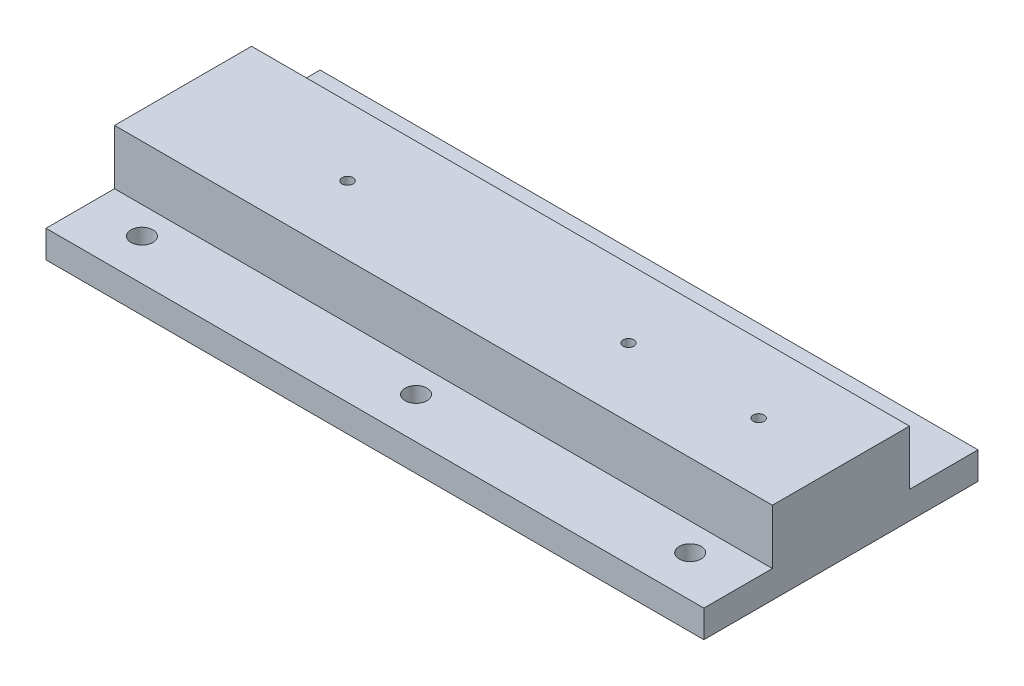
SolidWorks part; units mm, degrees
ref_plane "Front Plane" through (0, 0, 0) normal (0, 0, 1) x (1, 0, 0)
ref_plane "Top Plane" through (0, 0, 0) normal (0, 1, 0) x (1, 0, 0)
ref_plane "Right Plane" through (0, 0, 0) normal (1, 0, 0) x (0, 0, -1)
sketch "Sketch2" plane through (0, 0, 0) normal (0, 1, 0) x (1, 0, 0)
  line L0 (-46.8981, 34.5466) -> (-46.8981, -15.4534)
  line L1 (-46.8981, -15.4534) -> (73.1019, -15.4534)
  line L2 (73.1019, -15.4534) -> (73.1019, 34.5466)
  line L3 (73.1019, 34.5466) -> (-46.8981, 34.5466)
  dimension "D1" = 120
  dimension "D2" = 50
extrude "Boss-Extrude1" add sketch "Sketch2" along normal blind 15
sketch "Sketch3" plane through (0, 0, 0) normal (0, 1, 0) x (1, 0, 0)
  line L0 (74.3548, 9.5466) -> (-56.2815, 9.5466) construction
  line L1 (63.1019, 9.5466) -> (63.1019, 17.0466)
  line L2 (63.1019, 17.0466) -> (3.1019, 17.0466)
  line L3 (3.1019, 17.0466) -> (3.1019, 19.5466)
  line L4 (3.1019, 19.5466) -> (-36.8981, 19.5466)
  line L5 (-36.8981, 19.5466) -> (-36.8981, 9.5466)
  line L6 (-36.8981, 9.5466) -> (63.1019, 9.5466)
  line L7 (73.1019, -15.4534) -> (73.1019, 34.5466) construction
  line L9 (-46.8981, -15.4534) -> (73.1019, -15.4534) construction
  dimension "D1" = 60
  dimension "D2" = 40
  dimension "D3" = 10
  dimension "D4" = 25
  dimension "D5" = 10
  dimension "D6" = 7.5
revolve "Cut-Revolve8" cut sketch "Sketch3" angle 360 about L0
ref_plane "Ebene1" through (63.1019, 0, 0) normal (-1, 0, 0) x (0, 0, 1)
sketch "Skizze2" plane through (63.1019, 0, 0) normal (-1, 0, 0) x (0, 0, 1)
  line L0 (-22.101, 0) -> (5.7524, 0) construction
  line L1 (-2.0466, 0) -> (-17.0466, 0) construction
  line L2 (-9.5466, -15.2765) -> (-9.5466, 13.7911) construction
  line L3 (-4.5466, 0) -> (-2.0466, 0)
  line L5 (-34.5466, 15) -> (-34.5466, 0) construction
  line L6 (15.4534, 15) -> (15.4534, 0) construction
  line L7 (-6.3324, 3.83) -> (-4.7313, 5.75)
  arc A0 (-2.0466, 0) -> (-4.7313, 5.75) centre (-9.5466, 0) ccw
  arc A1 (-4.5466, 0) -> (-6.3324, 3.83) centre (-9.5466, 0) ccw
  dimension "D1" = 5.75
  dimension "D2" = 7.5
  dimension "D3" = 2.5
  dimension "D4" = 3.83
ref_plane "Ebene2" through (28.1019, 0, 0) normal (-1, 0, 0) x (0, 0, 1)
extrude "Aufsatz-Linear austragen3" add sketch "Skizze2" along normal blind 47.5
ref_plane "Ebene3" through (0, 0, -9.5466) normal (0, 0, 1) x (1, 0, 0)
mirror "Spiegeln1" about plane through (0, 0, -9.5466) normal (0, 0, 1) of "Aufsatz-Linear austragen3"
sketch "Skizze7" plane through (63.1019, 0, 0) normal (-1, 0, 0) x (0, 0, 1)
  line L0 (-4.5466, 0) -> (-14.5466, 0) construction
  circle A0 centre (-9.5466, 0) radius 7.5
  arc A1 (-4.7313, 5.75) -> (-14.362, 5.75) centre (-9.5466, 0) ccw construction
extrude "Schnitt-Linear austragen2" cut sketch "Skizze7" against normal blind 12.5 from surface starting at plane "Ebene2"
extrude "Schnitt-Linear austragen3" cut sketch "Skizze7<2>" along normal blind 10 contours A0
sketch "Skizze7<2>" plane through (63.1019, 0, 0) normal (-1, 0, 0) x (0, 0, 1) same geometry as "Skizze7"
sketch "Skizze8" plane through (0, 15, 0) normal (0, 1, 0) x (1, 0, 0)
  line L0 (91.3144, 9.5466) -> (-68.5218, 9.5466) construction
  line L1 (73.1019, 34.5466) -> (-46.8981, 34.5466) construction
  line L2 (-46.8981, -15.4534) -> (73.1019, -15.4534) construction
  line L3 (73.1019, -15.4534) -> (73.1019, 34.5466) construction
  line L4 (-46.8981, 34.5466) -> (-46.8981, -15.4534) construction
  circle A0 centre (58.1019, 9.5466) radius 1
  circle A1 centre (34.3519, 9.5466) radius 1
  circle A2 centre (-16.8981, 9.5466) radius 1
  dimension "D1" = 2
  dimension "D2" = 23.75
  dimension "D3" = 15
  dimension "D4" = 30
extrude "Schnitt-Linear austragen4" cut sketch "Skizze8" against normal up to next
sketch "Skizze9" plane through (-46.8981, 0, 0) normal (-1, 0, 0) x (0, 0, 1)
  line L0 (-34.5466, 5) -> (-22.0466, 5)
  line L1 (2.9534, 5) -> (2.9534, 15)
  line L2 (15.4534, 0) -> (-34.5466, 0) construction
  line L4 (2.9534, 5) -> (15.4534, 5)
  line L5 (15.4534, 15) -> (15.4534, 0) construction
  line L6 (-34.5466, 5) -> (-34.5466, 15)
  line L7 (-34.5466, 15) -> (15.4534, 15)
  line L8 (15.4534, 15) -> (15.4534, 5)
  line L9 (2.9534, 15) -> (-22.0466, 15)
  line L10 (-22.0466, 15) -> (-22.0466, 5)
  point P2 (3.0215, 5)
  point P8 (-22.4874, 5)
  line M8 (15.4534, 0) -> (15.4534, 15)
  line M9 (15.4534, 15) -> (-34.5466, 15)
  line M10 (-34.5466, 15) -> (-34.5466, 0)
  dimension "D1" = 5
  dimension "D2" = 12.5
  dimension "D3" = 12.5
extrude "Schnitt-Linear austragen5" cut sketch "Skizze9" against normal through all contours L10 L7 L0 M10 | L4 M9 M8 region at (-46.8981, 10, -28.2966) region at (-46.8981, 10, 9.2034)
sketch "Skizze10" plane through (0, 5, 0) normal (0, 1, 0) x (1, 0, 0)
  line L0 (73.1019, 34.5466) -> (73.1019, 22.0466) construction
  line L1 (73.1019, 34.5466) -> (-46.8981, 34.5466) construction
  circle A0 centre (63.1019, 27.0466) radius 2
  dimension "D1" = 4
  dimension "D2" = 10
  dimension "D3" = 7.5
extrude "Schnitt-Linear austragen7" cut sketch "Skizze10" against normal through all
sketch "Skizze11" plane through (0, 5, 0) normal (0, 1, 0) x (1, 0, 0)
  line L0 (80.5883, 9.5466) -> (-93.0916, 9.5466) construction
  line L1 (73.1019, 34.5466) -> (-46.8981, 34.5466) construction
  line L2 (73.1019, -15.4534) -> (-46.8981, -15.4534) construction
mirror "Spiegeln2" about plane through (0, 0, -9.5466) normal (0, 0, 1) of "Schnitt-Linear austragen7"
ref_plane "Ebene4" through (13.1019, 0, 0) normal (1, 0, 0) x (0, 0, -1)
mirror "Spiegeln3" about plane through (13.1019, 0, 0) normal (1, 0, 0) of "Schnitt-Linear austragen7", "Spiegeln2"
sketch "Skizze12" plane through (0, 5, 0) normal (0, 1, 0) x (1, 0, 0)
  line L0 (73.1019, -15.4534) -> (73.1019, 34.5466) construction
  line L1 (73.1019, 34.5466) -> (-46.8981, 34.5466) construction
  line L2 (73.1019, -15.4534) -> (-46.8981, -15.4534) construction
  circle A0 centre (13.1019, 27.0466) radius 2
  circle A1 centre (13.1019, -7.9534) radius 2
  circle A2 centre (63.1019, -7.9534) radius 2 construction
  dimension "D1" = 60
  dimension "D2" = 7.5
  dimension "D3" = 7.5
extrude "Schnitt-Linear austragen8" cut sketch "Skizze12" against normal blind 10
